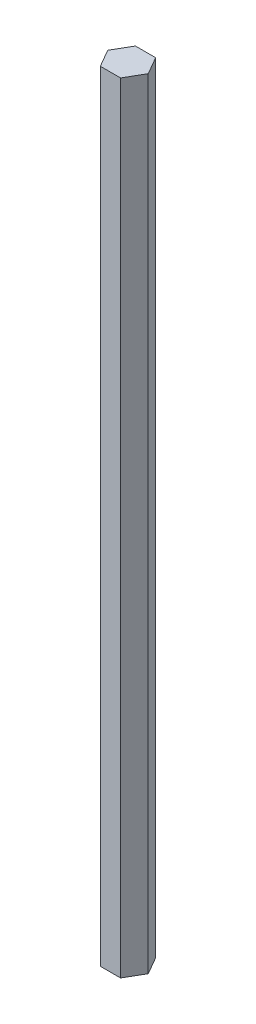
SolidWorks part; units mm, degrees
material "6061-T6 (SS)"
ref_plane "Front" through (0, 0, 0) normal (0, 0, 1) x (1, 0, 0)
ref_plane "Top" through (0, 0, 0) normal (0, 1, 0) x (1, 0, 0)
ref_plane "Right" through (0, 0, 0) normal (1, 0, 0) x (0, 0, -1)
sketch "Sketch1" plane through (0, 0, 0) normal (0, 1, 0) x (1, 0, 0)
  line L1 (2.8868, 0) -> (1.4434, 2.5)
  line L2 (1.4434, 2.5) -> (-1.4434, 2.5)
  line L3 (-1.4434, 2.5) -> (-2.8868, 0)
  line L4 (-2.8868, 0) -> (-1.4434, -2.5)
  line L5 (-1.4434, -2.5) -> (1.4434, -2.5)
  line L6 (1.4434, -2.5) -> (2.8868, 0)
  circle A0 centre (0, 0) radius 2.5 construction
  dimension "D1" = 5
extrude "Boss-Extrude1" add sketch "Sketch1" along normal mid plane 111.125
ref_axis "Axis1" through (0, 49.5981, 0) along (0, -1, 0)
